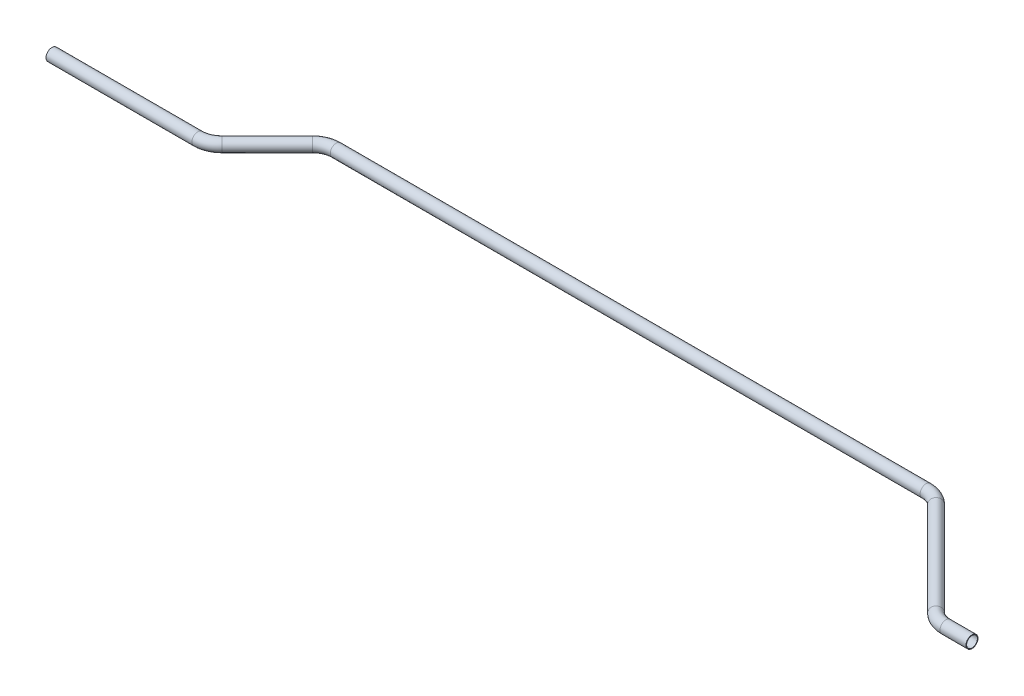
SolidWorks part; units mm, degrees
ref_plane "Front Plane" through (0, 0, 0) normal (0, 0, 1) x (1, 0, 0)
ref_plane "Top Plane" through (0, 0, 0) normal (0, 1, 0) x (1, 0, 0)
ref_plane "Right Plane" through (0, 0, 0) normal (1, 0, 0) x (0, 0, -1)
sketch "Sketch1" plane through (0, 0, 0) normal (0, 1, 0) x (1, 0, 0)
  line L0 (0, 0) -> (154.579, 0)
  line L1 (172.5395, 7.4395) -> (220.3985, 55.2985)
  line L2 (238.359, 62.738) -> (863.0866, 62.738)
  line L3 (881.0471, 55.2985) -> (980.4681, -44.1225)
  line L4 (998.4286, -51.562) -> (1026.0076, -51.562)
  arc A0 (980.4681, -44.1225) -> (998.4286, -51.562) centre (998.4286, -26.162) ccw
  arc A1 (863.0866, 62.738) -> (881.0471, 55.2985) centre (863.0866, 37.338) cw
  arc A2 (220.3985, 55.2985) -> (238.359, 62.738) centre (238.359, 37.338) cw
  arc A3 (154.579, 0) -> (172.5395, 7.4395) centre (154.579, 25.4) ccw
  point P9 (987.9076, -51.562)
  point P12 (873.6076, 62.738)
  point P15 (227.838, 62.738)
  point P18 (165.1, 0)
  dimension "D7" = 25.4
  dimension "D1" = 62.738
  dimension "D2" = 165.1
  dimension "D3" = 135
  dimension "D4" = 645.7696
  dimension "D5" = 38.1
  dimension "D6" = 114.3
ref_plane "Plane1" through (0, 0, 0) normal (1, 0, 0) x (0, 0, -1)
sketch "Sketch2" plane through (0, 0, 0) normal (1, 0, 0) x (0, 0, -1)
  circle A0 centre (0, 0) radius 6.35
  circle A1 centre (0, 0) radius 5.715
  dimension "D1" = 12.7
  dimension "D2" = 0.635
sweep "Sweep1" add profiles "Sketch2" path "Sketch1"
